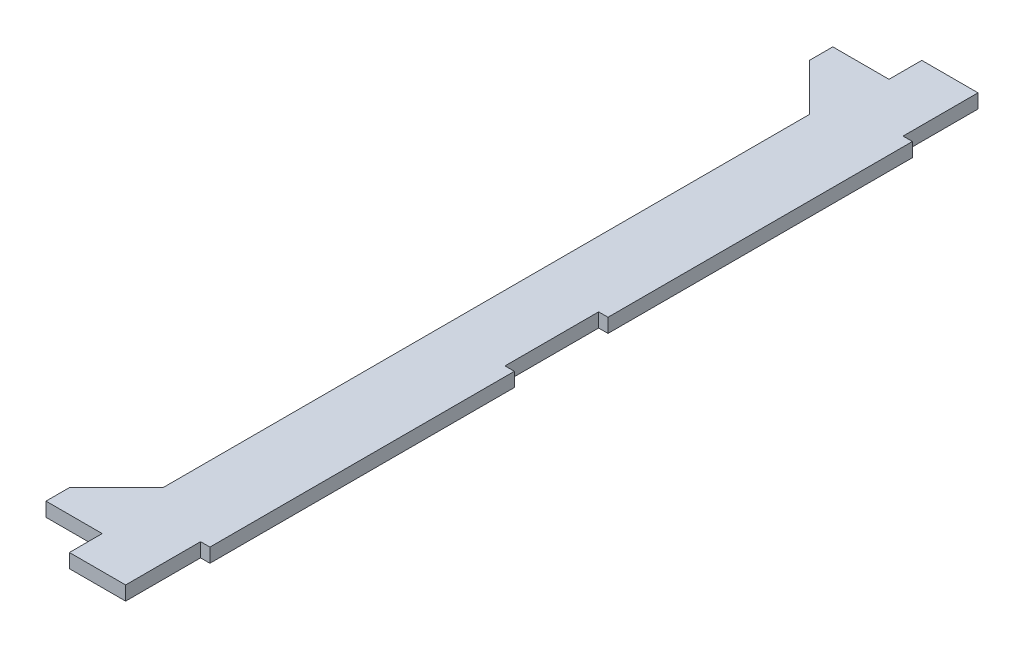
SolidWorks part; units mm, degrees
material "1023 Arkusz stali węglowej (SS)"
ref_plane "Płaszczyzna przednia" through (0, 0, 0) normal (0, 0, 1) x (1, 0, 0)
ref_plane "Płaszczyzna górna" through (0, 0, 0) normal (0, 1, 0) x (1, 0, 0)
ref_plane "Płaszczyzna prawa" through (0, 0, 0) normal (1, 0, 0) x (0, 0, -1)
sketch "Szkic1" plane through (0, 0, 0) normal (0, 1, 0) x (1, 0, 0)
  line L122 (452.8483, -47.8621) -> (450.8483, -47.8621)
  line L123 (452.8483, -47.8621) -> (452.8483, 17.1379)
  line L124 (450.8483, 17.1379) -> (450.8483, 27.1379)
  line L125 (450.8483, 17.1379) -> (452.8483, 17.1379)
  line L126 (436.8483, -41.8621) -> (436.8483, 27.1379)
  line L127 (426.8483, -51.8621) -> (436.8483, -41.8621)
  line L128 (426.8483, -56.8621) -> (426.8483, -51.8621)
  line L129 (450.8483, -63.8621) -> (450.8483, -47.8621)
  line L130 (438.8483, -63.8621) -> (450.8483, -63.8621)
  line L131 (438.8483, -63.8621) -> (438.8483, -56.8621)
  line L132 (426.8483, -56.8621) -> (438.8483, -56.8621)
  line L133 (452.8483, 102.1379) -> (450.8483, 102.1379)
  line L134 (452.8483, 102.1379) -> (452.8483, 37.1379)
  line L135 (450.8483, 37.1379) -> (450.8483, 27.1379)
  line L136 (450.8483, 37.1379) -> (452.8483, 37.1379)
  line L137 (436.8483, 96.1379) -> (436.8483, 27.1379)
  line L138 (426.8483, 106.1379) -> (436.8483, 96.1379)
  line L139 (426.8483, 111.1379) -> (426.8483, 106.1379)
  line L140 (450.8483, 118.1379) -> (450.8483, 102.1379)
  line L141 (438.8483, 118.1379) -> (450.8483, 118.1379)
  line L142 (438.8483, 118.1379) -> (438.8483, 111.1379)
  line L143 (426.8483, 111.1379) -> (438.8483, 111.1379)
extrude "Dodanie-wyciągnięcie1" add sketch "Szkic1" along normal blind 3
